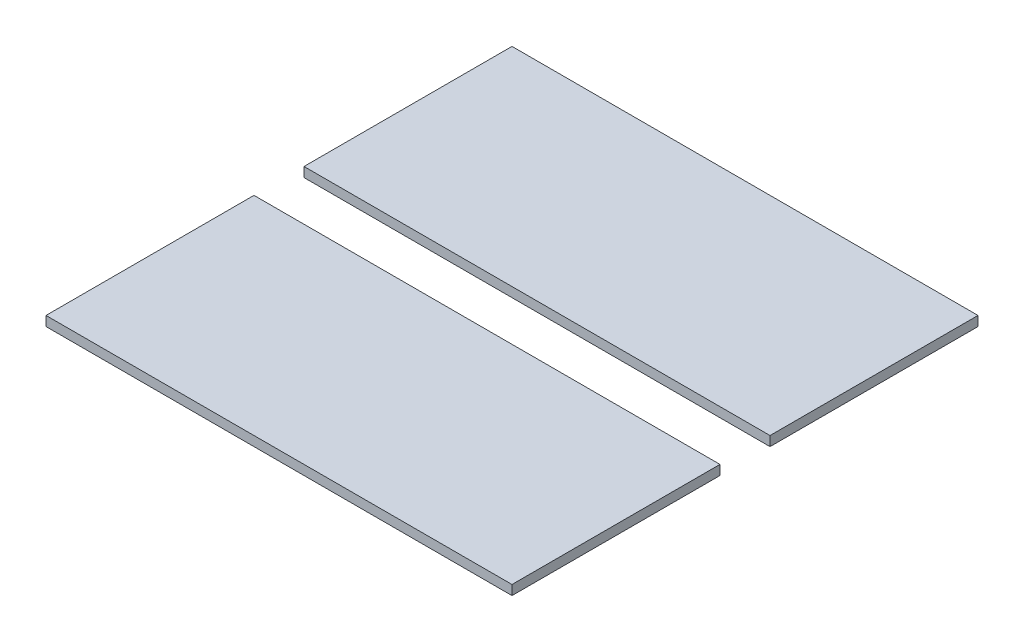
SolidWorks part; units mm, degrees
ref_plane "Front" through (0, 0, 0) normal (0, 0, 1) x (1, 0, 0)
ref_plane "Top" through (0, 0, 0) normal (0, 1, 0) x (1, 0, 0)
ref_plane "Right" through (0, 0, 0) normal (1, 0, 0) x (0, 0, -1)
sketch "Sketch1" plane through (0, 0, 0) normal (0, 1, 0) x (1, 0, 0)
  line L1 (-2454.275, 2454.275) -> (2454.275, 2454.275)
  line L2 (-2454.275, 2454.275) -> (-2454.275, -2454.275)
  line L3 (-2454.275, -2454.275) -> (2454.275, -2454.275)
  line L4 (2454.275, 2454.275) -> (2454.275, -2454.275)
  line L5 (-2454.275, 2454.275) -> (2454.275, -2454.275) construction
  line L6 (-2454.275, -2454.275) -> (2454.275, 2454.275) construction
  point P0 (0, 0)
  dimension "D1" = 4908.55
  dimension "D2" = 4908.55
extrude "Boss-Extrude1" add sketch "Sketch1" along normal blind 101.6
sketch "Sketch2" plane through (0, 101.6, 0) normal (0, 1, 0) x (1, 0, 0)
  line L0 (-2454.275, 2454.275) -> (-2454.275, -2454.275) construction
  line L1 (2454.275, -263.525) -> (-2454.275, -263.525)
  line L2 (2454.275, -263.525) -> (2454.275, 263.525)
  line L3 (2454.275, 263.525) -> (-2454.275, 263.525)
  line L4 (-2454.275, -263.525) -> (-2454.275, 263.525)
  line L5 (2454.275, -263.525) -> (-2454.275, 263.525) construction
  line L6 (2454.275, 263.525) -> (-2454.275, -263.525) construction
  point P0 (0, 0)
  dimension "D1" = 527.05
extrude "Cut-Extrude1" cut sketch "Sketch2" against normal through all
